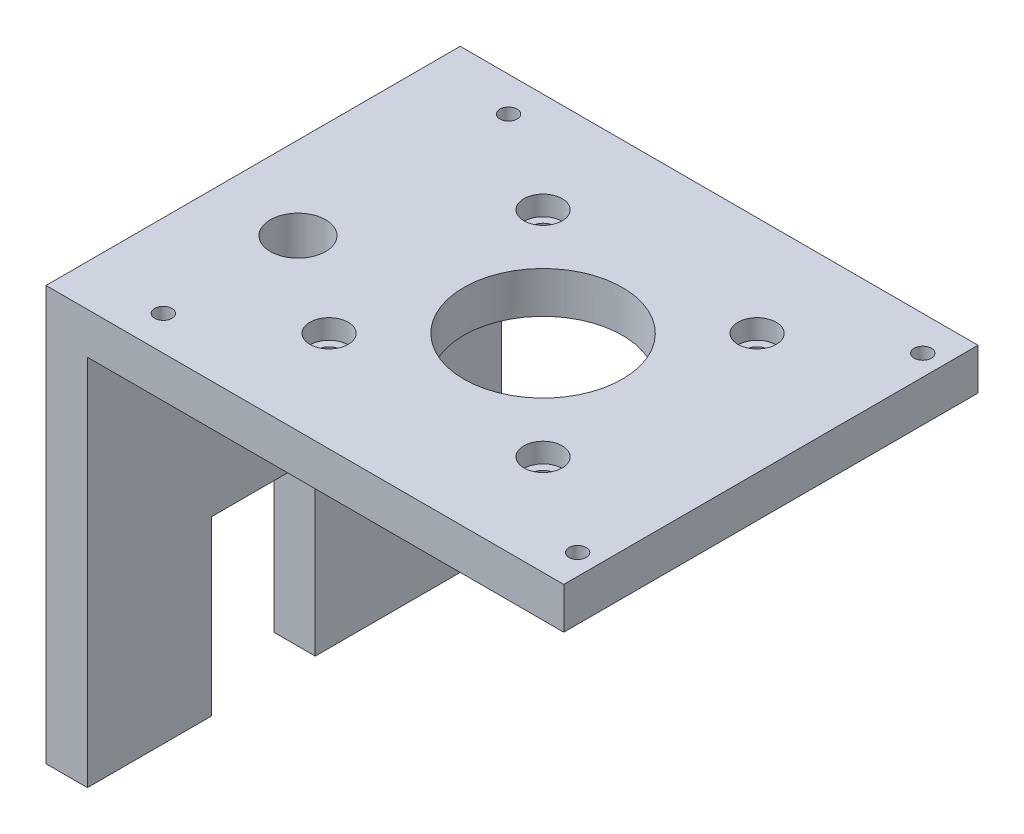
SolidWorks part; units mm, degrees
material "6061 Alloy"
ref_plane "Front Plane" through (0, 0, 0) normal (0, 0, 1) x (1, 0, 0)
ref_plane "Top Plane" through (0, 0, 0) normal (0, 1, 0) x (1, 0, 0)
ref_plane "Right Plane" through (0, 0, 0) normal (1, 0, 0) x (0, 0, -1)
sketch "Sketch1" plane through (0, 0, 0) normal (0, 0, 1) x (1, 0, 0)
  line L0 (0, 0) -> (6, 0)
  line L2 (0, 0) -> (0, 60)
  line L3 (0, 60) -> (75, 60)
  line L4 (75, 54) -> (75, 60)
  line L6 (6, 0) -> (6, 54)
  line L7 (6, 54) -> (75, 54)
  dimension "D1" = 75
  dimension "D2" = 6
  dimension "D3" = 6
  dimension "D4" = 60
extrude "Boss-Extrude1" add sketch "Sketch1" along normal blind 60
sketch "Sketch2" plane through (0, 60, 0) normal (0, 1, 0) x (1, 0, 0)
  line L0 (26.5, -45.5) -> (57.5, -45.5) construction
  line L1 (26.5, -45.5) -> (26.5, -14.5) construction
  line L2 (75, -60) -> (75, 0) construction
  line L6 (37.5, 0) -> (37.5, -60) construction
  line L7 (75, 0) -> (0, 0) construction
  line L8 (75, -60) -> (0, -60) construction
  circle A0 centre (42, -30) radius 11.5
  point P2 (26.5, -45.5)
  point P3 (42, -45.5)
  point P4 (26.5, -30)
  point P5 (57.5, -45.5)
  point P6 (26.5, -14.5)
  point P7 (57.5, -14.5)
  point P17 (37.5, -30)
  dimension "D1" = 23
  dimension "D2" = 31
  dimension "D3" = 31
  dimension "D6" = 33
  dimension "D4" = 2
  dimension "D5" = 2
extrude "Cut-Extrude1" cut sketch "Sketch2" against normal through all
ref_axis "Axis1" through (42, 54, 30) along (0, 1, 0)
hole_wizard "CBORE for #4 Socket Head Cap Screw1" positions "Sketch7" profile "Sketch6" counterbore size "#4" standard "Ansi Inch" end condition through all
sketch "Sketch7" plane through (0, 60, 0) normal (0, 1, 0) x (-1, 0, 0)
  line L0 (-26.5, 45.5) -> (-57.5, 45.5) construction
  line L1 (-26.5, 45.5) -> (-26.5, 14.5) construction
  point P0 (-26.5, 45.5)
  point P8 (-57.5, 45.5)
  point P9 (-26.5, 14.5)
  point P10 (-57.5, 14.5)
  point P34 (-42, 45.5)
  point P35 (-26.5, 30)
  dimension "D1" = 31
  dimension "D4" = 31
  dimension "D2" = 2
  dimension "D3" = 2
sketch "Sketch6" plane through (26.5, 60, 45.5) normal (1, 0, 0) x (0, 0, 1)
  line L0 (0, 0) -> (0, 60)
  line L1 (0, 60) -> (1.6319, 60)
  line L3 (1.6319, 60) -> (1.632, 2.8448)
  line L4 (1.632, 2.8448) -> (2.7788, 2.8448)
  line L5 (2.7788, 2.8448) -> (2.7788, 0)
  line L7 (2.7788, 0) -> (0, 0)
  line L11 (0, -6.35) -> (0, 107.95) construction
  dimension "Thru Hole Dia." = 3.2639
  dimension "Thru Hole Depth" = 60
  dimension "C'Bore Dia." = 5.5575
  dimension "C'Bore Depth" = 2.8448
hole_wizard "M3 Tapped Hole1" positions "Sketch9" profile "Sketch10" tap size "M3" standard "ISO"
sketch "Sketch9" plane through (0, 60, 0) normal (0, 1, 0) x (-1, 0, 0)
  line L0 (-12, 55) -> (-72, 55) construction
  line L1 (-12, 55) -> (-12, 5) construction
  line L16 (-42, 30) -> (-42, 62.1853) construction
  line L18 (-42, 30) -> (-7.0376, 30) construction
  point P1 (-12, 55)
  point P5 (-72, 55)
  point P6 (-12, 5)
  point P7 (-72, 5)
  point P83 (-42, 55)
  point P90 (-12, 30)
  dimension "D1" = 60
  dimension "D2" = 50
  dimension "D3" = 2
  dimension "D4" = 2
sketch "Sketch10" plane through (12, 60, 55) normal (1, 0, 0) x (0, 0, 1)
  line L0 (0, 0) -> (0, 9.2511)
  line L1 (0, 9.2511) -> (1.25, 8.5)
  line L2 (1.25, 8.5) -> (1.25, 0)
  line L5 (1.25, 0) -> (0, 0)
  line L10 (0, 9.2511) -> (-1.25, 8.5) construction
  line L11 (0, -6.35) -> (0, 107.95) construction
  dimension "Tap Drill Dia." = 2.5
  dimension "Tap Drill Depth" = 8.5
  dimension "Drill Angle" = 118
cosmetic thread "Hole Thread1" parameters "D1"=6, "D2"=3
cosmetic thread "Hole Thread2" parameters "D1"=6, "D2"=3
cosmetic thread "Hole Thread3" parameters "D1"=6, "D2"=3
cosmetic thread "Hole Thread4" parameters "D1"=6, "D2"=3
sketch "Sketch11" plane through (0, 60, 0) normal (0, 1, 0) x (1, 0, 0)
  line L0 (75, -60) -> (0, -60) construction
  line L1 (0, -60) -> (0, 0) construction
  circle A0 centre (12, -35.5) radius 4
  dimension "D2" = 8
  dimension "D1" = 12
  dimension "D3" = 24.5
extrude "Cut-Extrude2" cut sketch "Sketch11" against normal through all
sketch "Sketch12" plane through (6, 0, 0) normal (1, 0, 0) x (0, 0, -1)
  line L0 (-60, 0) -> (0, 0) construction
  line L1 (-42, 0) -> (-27, 0)
  line L2 (-42, 0) -> (-42, 25)
  line L3 (-42, 25) -> (-27, 25)
  line L4 (-27, 0) -> (-27, 25)
  line L5 (-34.5, 28.313) -> (-34.5, -2.9931) construction
  line L6 (-60, 0) -> (-60, 54) construction
  point P8 (-34.5, 25)
  dimension "D1" = 25.5
  dimension "D2" = 15
  dimension "D3" = 25
extrude "Cut-Extrude3" cut sketch "Sketch12" against normal through all
